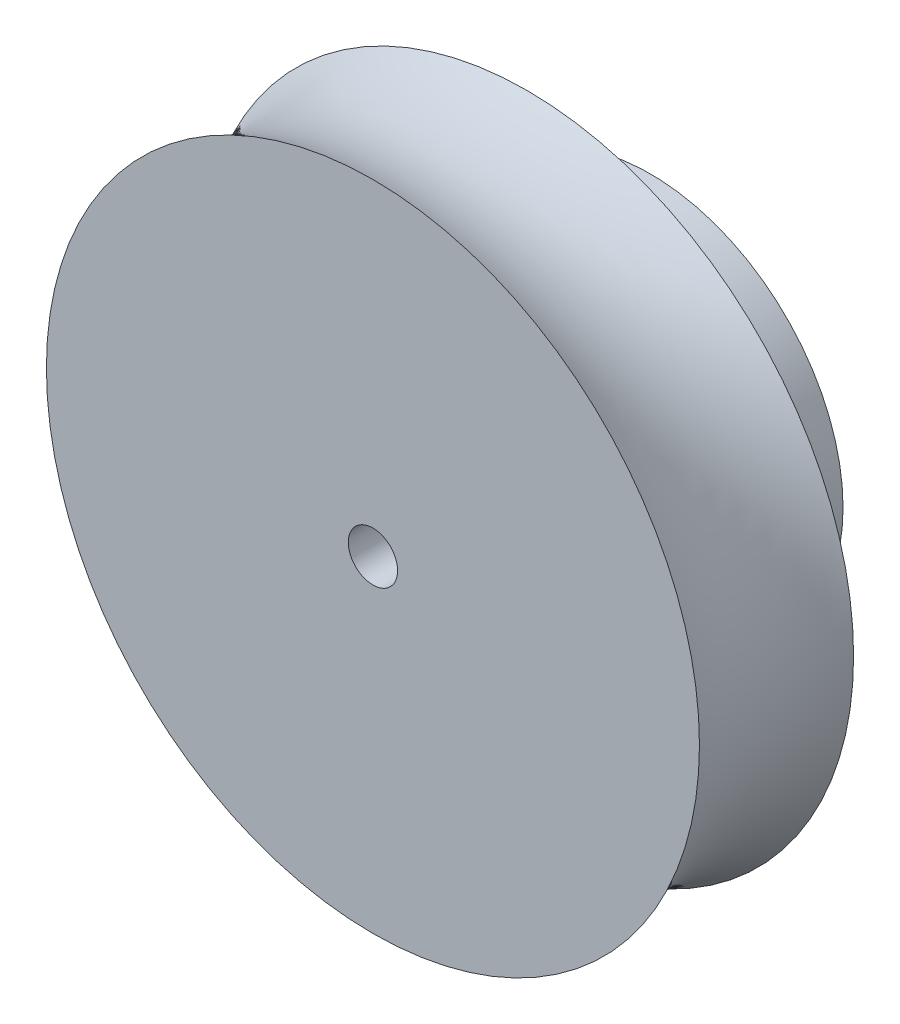
SolidWorks part; units mm, degrees
ref_plane "Front Plane" through (0, 0, 0) normal (0, 0, 1) x (1, 0, 0)
ref_plane "Top Plane" through (0, 0, 0) normal (0, 1, 0) x (1, 0, 0)
ref_plane "Right Plane" through (0, 0, 0) normal (1, 0, 0) x (0, 0, -1)
sketch "Sketch2" plane through (0, 0, 0) normal (0, 1, 0) x (1, 0, 0)
  line L0 (0, 5) -> (0, -5)
  line L1 (0, 5) -> (21.1839, 5)
  line L2 (0, -5) -> (21.1839, -5)
  line L3 (0, 0) -> (20, 0) construction
  arc A0 (21.1839, 5) -> (21.1839, -5) centre (31.15, 0) ccw
  point P4 (0, 0)
  point P11 (20, 0)
  dimension "D3" = 11.15
  dimension "D1" = 10
  dimension "D2" = 20
revolve "Revolve1" add sketch "Sketch2" angle 360 about L0
sketch "Sketch3" plane through (0, 0, -5) normal (0, 0, -1) x (-1, 0, 0)
  circle A0 centre (0, 0) radius 1.6
  circle A2 centre (0, 0) radius 21.1839 construction
  circle A28 centre (0, 0) radius 21.1839 construction
  point P0 (0, 0)
  point P26 (0, 0)
  point P45 (0, 0)
  point P48 (0, 0)
  dimension "D1" = 3.2
extrude "Cut-Extrude1" cut sketch "Sketch3" against normal through all
sketch "Sketch4" plane through (0, 0, -5) normal (0, 0, -1) x (-1, 0, 0)
  circle A0 centre (0, 0) radius 12.5
  circle A1 centre (0, 0) radius 1.75
  dimension "D1" = 25
extrude "Boss-Extrude1" add sketch "Sketch4" along normal blind 8
sketch "Sketch5" plane through (0, 0, 0) normal (1, 0, 0) x (0, 0, -1)
  line L0 (5, 0) -> (13, 0) construction
  line L1 (5, -21.1839) -> (5, 21.1839) construction
  line L2 (13, -12.5) -> (13, 12.5) construction
  circle A0 centre (9, 0) radius 1.65
  point P10 (9, 0)
  dimension "D1" = 3.3
extrude "Cut-Extrude2" cut sketch "Sketch5" against normal through all both and the other way through all
ref_plane "Plane1" through (-3.2, 0, 0) normal (1, 0, 0) x (0, 0, -1)
sketch "Sketch6" plane through (-3.2, 0, 0) normal (1, 0, 0) x (0, 0, -1)
  line L0 (10.6454, 2.85) -> (13, 2.85)
  line L1 (7.3546, -2.85) -> (10.6454, -2.85)
  line L2 (10.6454, -2.85) -> (12.2909, 0) construction
  line L3 (12.2909, 0) -> (10.6454, 2.85) construction
  line L4 (10.6454, 2.85) -> (7.3546, 2.85)
  line L5 (7.3546, 2.85) -> (5.7091, 0)
  line L6 (5.7091, 0) -> (7.3546, -2.85)
  line L7 (13, -12.5) -> (13, 12.5) construction
  line L8 (13, 2.85) -> (13, -2.85)
  line L9 (13, -2.85) -> (10.6454, -2.85)
  circle A0 centre (9, 0) radius 2.85 construction
  dimension "D1" = 5.7
extrude "Cut-Extrude3" cut sketch "Sketch6" against normal blind 2.7
ref_plane "Plane2" through (3.2, 0, 0) normal (1, 0, 0) x (0, 0, -1)
sketch "Sketch7" plane through (3.2, 0, 0) normal (1, 0, 0) x (0, 0, -1)
  line L7 (13, 2.85) -> (10.6454, 2.85)
  line L8 (13, -2.85) -> (13, 2.85)
  line L9 (10.6454, -2.85) -> (13, -2.85)
  line L10 (7.3546, -2.85) -> (10.6454, -2.85)
  line L11 (5.7091, 0) -> (7.3546, -2.85)
  line L12 (7.3546, 2.85) -> (5.7091, 0)
  line L13 (10.6454, 2.85) -> (7.3546, 2.85)
  line L14 (13, 2.85) -> (10.6454, 2.85)
  line L15 (13, -2.85) -> (13, 2.85)
  line L16 (10.6454, -2.85) -> (13, -2.85)
  line L17 (7.3546, -2.85) -> (10.6454, -2.85)
  line L18 (5.7091, 0) -> (7.3546, -2.85)
  line L19 (7.3546, 2.85) -> (5.7091, 0)
  line L20 (10.6454, 2.85) -> (7.3546, 2.85)
  dimension "D1" = 0
extrude "Cut-Extrude4" cut sketch "Sketch7" along normal blind 2.7
